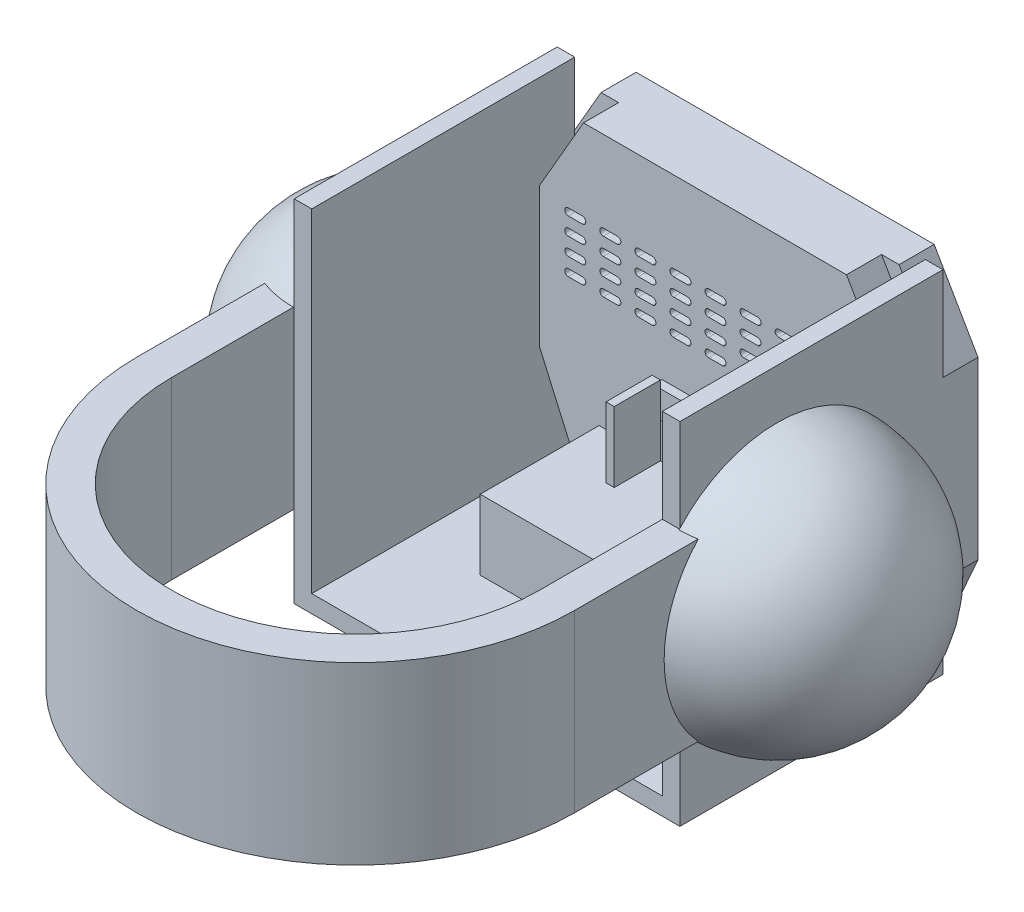
SolidWorks part; units mm, degrees
ref_plane "前视基准面" through (0, 0, 0) normal (0, 0, 1) x (1, 0, 0)
ref_plane "上视基准面" through (0, 0, 0) normal (0, 1, 0) x (1, 0, 0)
ref_plane "右视基准面" through (0, 0, 0) normal (1, 0, 0) x (0, 0, -1)
sketch "草图1" plane through (0, 0, 0) normal (0, 0, 1) x (1, 0, 0)
  line L0 (25, 43.3013) -> (175, 43.3013)
  line L1 (175, 43.3013) -> (200, 0)
  line L2 (200, 0) -> (200, -80)
  line L4 (0, 0) -> (0, -80)
  line L5 (25, 43.3013) -> (0, 0)
  line L6 (175, -136.6987) -> (200, -80)
  line L7 (25, -136.6987) -> (175, -136.6987)
  line L8 (25, -136.6987) -> (0, -80)
  point P10 (200, -40)
  point P13 (0, -40)
  dimension "D1" = 150
  dimension "D2" = 25
  dimension "D3" = 25
  dimension "D4" = 180
  dimension "D5" = 80
  dimension "D6" = 50
  dimension "D7" = 56.6987
extrude "凸台-拉伸1" add sketch "草图1" along normal blind 20
sketch "草图2" plane through (0, 0, 20) normal (0, 0, 1) x (1, 0, 0)
  line L0 (16.3073, -5) -> (24.3073, -5) construction
  line L1 (16.3073, -3) -> (24.3073, -3)
  line L2 (16.3073, -7) -> (24.3073, -7)
  line L3 (36.3073, -5) -> (44.3073, -5) construction
  line L4 (36.3073, -3) -> (44.3073, -3)
  line L5 (36.3073, -7) -> (44.3073, -7)
  line L6 (56.3073, -5) -> (64.3073, -5) construction
  line L7 (56.3073, -3) -> (64.3073, -3)
  line L8 (56.3073, -7) -> (64.3073, -7)
  line L9 (76.3073, -5) -> (84.3073, -5) construction
  line L10 (76.3073, -3) -> (84.3073, -3)
  line L11 (76.3073, -7) -> (84.3073, -7)
  line L12 (96.3073, -5) -> (104.3073, -5) construction
  line L13 (96.3073, -3) -> (104.3073, -3)
  line L14 (96.3073, -7) -> (104.3073, -7)
  line L15 (116.3073, -5) -> (124.3073, -5) construction
  line L16 (116.3073, -3) -> (124.3073, -3)
  line L17 (116.3073, -7) -> (124.3073, -7)
  line L18 (136.3073, -5) -> (144.3073, -5) construction
  line L19 (136.3073, -3) -> (144.3073, -3)
  line L20 (136.3073, -7) -> (144.3073, -7)
  line L21 (156.3073, -5) -> (164.3073, -5) construction
  line L22 (156.3073, -3) -> (164.3073, -3)
  line L23 (156.3073, -7) -> (164.3073, -7)
  line L24 (176.3073, -5) -> (184.3073, -5) construction
  line L25 (176.3073, -3) -> (184.3073, -3)
  line L26 (176.3073, -7) -> (184.3073, -7)
  line L27 (16.3073, -15) -> (24.3073, -15) construction
  line L28 (16.3073, -13) -> (24.3073, -13)
  line L29 (16.3073, -17) -> (24.3073, -17)
  line L30 (16.3073, -25) -> (24.3073, -25) construction
  line L31 (16.3073, -23) -> (24.3073, -23)
  line L32 (16.3073, -27) -> (24.3073, -27)
  line L33 (16.3073, -35) -> (24.3073, -35) construction
  line L34 (16.3073, -33) -> (24.3073, -33)
  line L35 (16.3073, -37) -> (24.3073, -37)
  line L36 (36.3073, -13) -> (44.3073, -13)
  line L37 (36.3073, -17) -> (44.3073, -17)
  line L38 (36.3073, -15) -> (44.3073, -15) construction
  line L39 (36.3073, -25) -> (44.3073, -25) construction
  line L40 (36.3073, -23) -> (44.3073, -23)
  line L41 (36.3073, -27) -> (44.3073, -27)
  line L42 (36.3073, -35) -> (44.3073, -35) construction
  line L43 (36.3073, -33) -> (44.3073, -33)
  line L44 (36.3073, -37) -> (44.3073, -37)
  line L45 (56.3073, -13) -> (64.3073, -13)
  line L46 (56.3073, -17) -> (64.3073, -17)
  line L47 (56.3073, -15) -> (64.3073, -15) construction
  line L48 (56.3073, -25) -> (64.3073, -25) construction
  line L49 (56.3073, -23) -> (64.3073, -23)
  line L50 (56.3073, -27) -> (64.3073, -27)
  line L51 (56.3073, -35) -> (64.3073, -35) construction
  line L52 (56.3073, -33) -> (64.3073, -33)
  line L53 (56.3073, -37) -> (64.3073, -37)
  line L54 (76.3073, -13) -> (84.3073, -13)
  line L55 (76.3073, -17) -> (84.3073, -17)
  line L56 (76.3073, -15) -> (84.3073, -15) construction
  line L57 (76.3073, -25) -> (84.3073, -25) construction
  line L58 (76.3073, -23) -> (84.3073, -23)
  line L59 (76.3073, -27) -> (84.3073, -27)
  line L60 (76.3073, -35) -> (84.3073, -35) construction
  line L61 (76.3073, -33) -> (84.3073, -33)
  line L62 (76.3073, -37) -> (84.3073, -37)
  line L63 (96.3073, -13) -> (104.3073, -13)
  line L64 (96.3073, -17) -> (104.3073, -17)
  line L65 (96.3073, -15) -> (104.3073, -15) construction
  line L66 (96.3073, -25) -> (104.3073, -25) construction
  line L67 (96.3073, -23) -> (104.3073, -23)
  line L68 (96.3073, -27) -> (104.3073, -27)
  line L69 (96.3073, -35) -> (104.3073, -35) construction
  line L70 (96.3073, -33) -> (104.3073, -33)
  line L71 (96.3073, -37) -> (104.3073, -37)
  line L72 (116.3073, -13) -> (124.3073, -13)
  line L73 (116.3073, -17) -> (124.3073, -17)
  line L74 (116.3073, -15) -> (124.3073, -15) construction
  line L75 (116.3073, -25) -> (124.3073, -25) construction
  line L76 (116.3073, -23) -> (124.3073, -23)
  line L77 (116.3073, -27) -> (124.3073, -27)
  line L78 (116.3073, -35) -> (124.3073, -35) construction
  line L79 (116.3073, -33) -> (124.3073, -33)
  line L80 (116.3073, -37) -> (124.3073, -37)
  line L81 (136.3073, -13) -> (144.3073, -13)
  line L82 (136.3073, -17) -> (144.3073, -17)
  line L83 (136.3073, -15) -> (144.3073, -15) construction
  line L84 (136.3073, -25) -> (144.3073, -25) construction
  line L85 (136.3073, -23) -> (144.3073, -23)
  line L86 (136.3073, -27) -> (144.3073, -27)
  line L87 (136.3073, -35) -> (144.3073, -35) construction
  line L88 (136.3073, -33) -> (144.3073, -33)
  line L89 (136.3073, -37) -> (144.3073, -37)
  line L90 (156.3073, -13) -> (164.3073, -13)
  line L91 (156.3073, -17) -> (164.3073, -17)
  line L92 (156.3073, -15) -> (164.3073, -15) construction
  line L93 (156.3073, -25) -> (164.3073, -25) construction
  line L94 (156.3073, -23) -> (164.3073, -23)
  line L95 (156.3073, -27) -> (164.3073, -27)
  line L96 (156.3073, -35) -> (164.3073, -35) construction
  line L97 (156.3073, -33) -> (164.3073, -33)
  line L98 (156.3073, -37) -> (164.3073, -37)
  line L99 (176.3073, -13) -> (184.3073, -13)
  line L100 (176.3073, -17) -> (184.3073, -17)
  line L101 (176.3073, -15) -> (184.3073, -15) construction
  line L102 (176.3073, -25) -> (184.3073, -25) construction
  line L103 (176.3073, -23) -> (184.3073, -23)
  line L104 (176.3073, -27) -> (184.3073, -27)
  line L105 (176.3073, -35) -> (184.3073, -35) construction
  line L106 (176.3073, -33) -> (184.3073, -33)
  line L107 (176.3073, -37) -> (184.3073, -37)
  line L108 (0, 0) -> (0, -80) construction
  arc A0 (16.3073, -3) -> (16.3073, -7) centre (16.3073, -5) ccw
  arc A1 (24.3073, -7) -> (24.3073, -3) centre (24.3073, -5) ccw
  arc A2 (36.3073, -3) -> (36.3073, -7) centre (36.3073, -5) ccw
  arc A3 (44.3073, -7) -> (44.3073, -3) centre (44.3073, -5) ccw
  arc A4 (56.3073, -3) -> (56.3073, -7) centre (56.3073, -5) ccw
  arc A5 (64.3073, -7) -> (64.3073, -3) centre (64.3073, -5) ccw
  arc A6 (76.3073, -3) -> (76.3073, -7) centre (76.3073, -5) ccw
  arc A7 (84.3073, -7) -> (84.3073, -3) centre (84.3073, -5) ccw
  arc A8 (96.3073, -3) -> (96.3073, -7) centre (96.3073, -5) ccw
  arc A9 (104.3073, -7) -> (104.3073, -3) centre (104.3073, -5) ccw
  arc A10 (116.3073, -3) -> (116.3073, -7) centre (116.3073, -5) ccw
  arc A11 (124.3073, -7) -> (124.3073, -3) centre (124.3073, -5) ccw
  arc A12 (136.3073, -3) -> (136.3073, -7) centre (136.3073, -5) ccw
  arc A13 (144.3073, -7) -> (144.3073, -3) centre (144.3073, -5) ccw
  arc A14 (156.3073, -3) -> (156.3073, -7) centre (156.3073, -5) ccw
  arc A15 (164.3073, -7) -> (164.3073, -3) centre (164.3073, -5) ccw
  arc A16 (176.3073, -3) -> (176.3073, -7) centre (176.3073, -5) ccw
  arc A17 (184.3073, -7) -> (184.3073, -3) centre (184.3073, -5) ccw
  arc A18 (16.3073, -13) -> (16.3073, -17) centre (16.3073, -15) ccw
  arc A19 (24.3073, -17) -> (24.3073, -13) centre (24.3073, -15) ccw
  arc A20 (16.3073, -23) -> (16.3073, -27) centre (16.3073, -25) ccw
  arc A21 (24.3073, -27) -> (24.3073, -23) centre (24.3073, -25) ccw
  arc A22 (16.3073, -33) -> (16.3073, -37) centre (16.3073, -35) ccw
  arc A23 (24.3073, -37) -> (24.3073, -33) centre (24.3073, -35) ccw
  arc A24 (44.3073, -17) -> (44.3073, -13) centre (44.3073, -15) ccw
  arc A25 (36.3073, -13) -> (36.3073, -17) centre (36.3073, -15) ccw
  arc A26 (36.3073, -23) -> (36.3073, -27) centre (36.3073, -25) ccw
  arc A27 (44.3073, -27) -> (44.3073, -23) centre (44.3073, -25) ccw
  arc A28 (36.3073, -33) -> (36.3073, -37) centre (36.3073, -35) ccw
  arc A29 (44.3073, -37) -> (44.3073, -33) centre (44.3073, -35) ccw
  arc A30 (64.3073, -17) -> (64.3073, -13) centre (64.3073, -15) ccw
  arc A31 (56.3073, -13) -> (56.3073, -17) centre (56.3073, -15) ccw
  arc A32 (56.3073, -23) -> (56.3073, -27) centre (56.3073, -25) ccw
  arc A33 (64.3073, -27) -> (64.3073, -23) centre (64.3073, -25) ccw
  arc A34 (56.3073, -33) -> (56.3073, -37) centre (56.3073, -35) ccw
  arc A35 (64.3073, -37) -> (64.3073, -33) centre (64.3073, -35) ccw
  arc A36 (84.3073, -17) -> (84.3073, -13) centre (84.3073, -15) ccw
  arc A37 (76.3073, -13) -> (76.3073, -17) centre (76.3073, -15) ccw
  arc A38 (76.3073, -23) -> (76.3073, -27) centre (76.3073, -25) ccw
  arc A39 (84.3073, -27) -> (84.3073, -23) centre (84.3073, -25) ccw
  arc A40 (76.3073, -33) -> (76.3073, -37) centre (76.3073, -35) ccw
  arc A41 (84.3073, -37) -> (84.3073, -33) centre (84.3073, -35) ccw
  arc A42 (104.3073, -17) -> (104.3073, -13) centre (104.3073, -15) ccw
  arc A43 (96.3073, -13) -> (96.3073, -17) centre (96.3073, -15) ccw
  arc A44 (96.3073, -23) -> (96.3073, -27) centre (96.3073, -25) ccw
  arc A45 (104.3073, -27) -> (104.3073, -23) centre (104.3073, -25) ccw
  arc A46 (96.3073, -33) -> (96.3073, -37) centre (96.3073, -35) ccw
  arc A47 (104.3073, -37) -> (104.3073, -33) centre (104.3073, -35) ccw
  arc A48 (124.3073, -17) -> (124.3073, -13) centre (124.3073, -15) ccw
  arc A49 (116.3073, -13) -> (116.3073, -17) centre (116.3073, -15) ccw
  arc A50 (116.3073, -23) -> (116.3073, -27) centre (116.3073, -25) ccw
  arc A51 (124.3073, -27) -> (124.3073, -23) centre (124.3073, -25) ccw
  arc A52 (116.3073, -33) -> (116.3073, -37) centre (116.3073, -35) ccw
  arc A53 (124.3073, -37) -> (124.3073, -33) centre (124.3073, -35) ccw
  arc A54 (144.3073, -17) -> (144.3073, -13) centre (144.3073, -15) ccw
  arc A55 (136.3073, -13) -> (136.3073, -17) centre (136.3073, -15) ccw
  arc A56 (136.3073, -23) -> (136.3073, -27) centre (136.3073, -25) ccw
  arc A57 (144.3073, -27) -> (144.3073, -23) centre (144.3073, -25) ccw
  arc A58 (136.3073, -33) -> (136.3073, -37) centre (136.3073, -35) ccw
  arc A59 (144.3073, -37) -> (144.3073, -33) centre (144.3073, -35) ccw
  arc A60 (164.3073, -17) -> (164.3073, -13) centre (164.3073, -15) ccw
  arc A61 (156.3073, -13) -> (156.3073, -17) centre (156.3073, -15) ccw
  arc A62 (156.3073, -23) -> (156.3073, -27) centre (156.3073, -25) ccw
  arc A63 (164.3073, -27) -> (164.3073, -23) centre (164.3073, -25) ccw
  arc A64 (156.3073, -33) -> (156.3073, -37) centre (156.3073, -35) ccw
  arc A65 (164.3073, -37) -> (164.3073, -33) centre (164.3073, -35) ccw
  arc A66 (184.3073, -17) -> (184.3073, -13) centre (184.3073, -15) ccw
  arc A67 (176.3073, -13) -> (176.3073, -17) centre (176.3073, -15) ccw
  arc A68 (176.3073, -23) -> (176.3073, -27) centre (176.3073, -25) ccw
  arc A69 (184.3073, -27) -> (184.3073, -23) centre (184.3073, -25) ccw
  arc A70 (176.3073, -33) -> (176.3073, -37) centre (176.3073, -35) ccw
  arc A71 (184.3073, -37) -> (184.3073, -33) centre (184.3073, -35) ccw
  point P2 (20.3073, -5)
  point P14 (40.3073, -5)
  point P21 (60.3073, -5)
  point P28 (80.3073, -5)
  point P35 (100.3073, -5)
  point P42 (120.3073, -5)
  point P49 (140.3073, -5)
  point P56 (160.3073, -5)
  point P63 (180.3073, -5)
  point P69 (20.3073, -15)
  point P76 (20.3073, -25)
  point P83 (20.3073, -35)
  point P90 (40.3073, -15)
  point P97 (40.3073, -25)
  point P104 (40.3073, -35)
  point P111 (60.3073, -15)
  point P118 (60.3073, -25)
  point P125 (60.3073, -35)
  point P132 (80.3073, -15)
  point P139 (80.3073, -25)
  point P146 (80.3073, -35)
  point P153 (100.3073, -15)
  point P160 (100.3073, -25)
  point P167 (100.3073, -35)
  point P174 (120.3073, -15)
  point P181 (120.3073, -25)
  point P188 (120.3073, -35)
  point P195 (140.3073, -15)
  point P202 (140.3073, -25)
  point P209 (140.3073, -35)
  point P216 (160.3073, -15)
  point P223 (160.3073, -25)
  point P230 (160.3073, -35)
  point P237 (180.3073, -15)
  point P244 (180.3073, -25)
  point P251 (180.3073, -35)
  dimension "D1" = 8
  dimension "D2" = 4
  dimension "D3" = 5
  dimension "D7" = 20.3073
  dimension "D8" = 20
  dimension "D9" = 20
  dimension "D10" = 10
  dimension "D4" = 9
  dimension "D5" = 4
  dimension "D6" = 9
extrude "切除-拉伸1" cut sketch "草图2" against normal through all
sketch "草图4" plane through (0, 43.3013, 0) normal (0, 1, 0) x (1, 0, 0)
  line L0 (200, -20) -> (200, 0) construction
  line L1 (0, 0) -> (200, 0)
  line L2 (0, 0) -> (0, -150)
  line L3 (0, -150) -> (200, -150)
  line L4 (200, 0) -> (200, -150)
  dimension "D1" = 150
sketch "草图5" plane through (0, 0, 0) normal (-1, 0, 0) x (0, 0, 1)
  line L1 (0, 53.3013) -> (150, 53.3013)
  line L2 (0, 53.3013) -> (0, -136.6987)
  line L3 (0, -136.6987) -> (150, -136.6987)
  line L5 (20, -136.6987) -> (0, -136.6987) construction
  line L6 (0, -80) -> (0, -136.6987) construction
  line L7 (150, 53.3013) -> (150, -136.6987)
  dimension "D1" = 190
  dimension "D2" = 150
sketch "草图6" plane through (200, 0, 0) normal (1, 0, 0) x (0, 0, -1)
  line L0 (-20, -136.6987) -> (0, -136.6987) construction
  line L1 (-150, 53.3013) -> (0, 53.3013)
  line L2 (-150, 53.3013) -> (-150, -136.6987)
  line L3 (-150, -136.6987) -> (0, -136.6987)
  line L4 (0, 53.3013) -> (0, -136.6987)
  line L9 (0, -80) -> (0, 0) construction
  dimension "D1" = 150
  dimension "D2" = 190
extrude "凸台-拉伸8" add sketch "草图5" along normal blind 10
extrude "凸台-拉伸5" add sketch "草图6" along normal blind 10
sketch "草图7" plane through (0, 0, 0) normal (0, 1, 0) x (1, 0, 0)
  line L0 (-9.9985, -94.5873) -> (-29.9585, -94.5873)
  line L2 (-29.9585, -94.5873) -> (-29.9585, -220)
  line L3 (-9.9985, -114.5458) -> (-10, -114.5458)
  line L4 (-10, -114.5458) -> (-10, -220)
  line L5 (219.9585, -94.5873) -> (219.9585, -220)
  line L6 (199.9985, -94.5873) -> (219.9585, -94.5873)
  line L7 (200, -114.5458) -> (200, -220)
  line L8 (199.9985, -114.5458) -> (200, -114.5458)
  line L9 (-9.9985, -114.5458) -> (-9.9985, -94.5873)
  line L10 (200, -114.5458) -> (199.9985, -94.5873)
  line L11 (200, 0) -> (200, -150) construction
  line L12 (-10, -150) -> (-10, 0) construction
  line L13 (0, -150) -> (200, -150) construction
  arc A1 (-29.9585, -220) -> (219.9585, -220) centre (95, -220) ccw
  arc A2 (-10, -220) -> (200, -220) centre (95, -220) ccw
  point P9 (100, -200.4127)
  dimension "D1" = 19.96
  dimension "D6" = 105
  dimension "D4" = 70
  dimension "D3" = 19.96
  dimension "D2" = 125.4127
  dimension "D5" = 249.917
extrude "凸台-拉伸6" add sketch "草图7" against normal blind 100 contours A2 L4 L9 L0 L2 A1 L5 L6 L10 L7 region at (-13.5361, 0, 104.5665)
sketch "草图8" plane through (0, -136.6987, 0) normal (0, -1, 0) x (1, 0, 0)
  line L1 (-10, 150) -> (210, 150)
  line L3 (-10, 0) -> (210, 0)
  line L4 (210, 150) -> (210, 0)
  line L5 (0, 150) -> (200, 150) construction
  line L7 (-10, 0) -> (-10, 150)
extrude "凸台-拉伸7" add sketch "草图8" along normal blind 10
sketch "草图9" plane through (0, 0, 0) normal (0, 0, -1) x (-1, 0, 0)
  line L0 (-210, 0) -> (-210, -100)
  line L1 (-210, -100) -> (-189.4093, -146.6987)
  line L2 (10, -146.6987) -> (-210, -146.6987) construction
  line L3 (-189.4093, -146.6987) -> (-10.5907, -146.6987)
  line L4 (-200, 0) -> (-175, 43.3013) construction
  line L5 (-210, 0) -> (-185, 43.3013)
  line L6 (0, 43.3013) -> (-200, 43.3013) construction
  line L7 (-185, 43.3013) -> (-15, 43.3013)
  line L8 (10, -100) -> (-10.5907, -146.6987)
  line L9 (10, 0) -> (10, -100)
  line L10 (10, 0) -> (-15, 43.3013)
  line L11 (-175, -136.6987) -> (-200, -80) construction
  line L12 (10, 53.3013) -> (10, -146.6987) construction
  line L13 (0, -80) -> (-25, -136.6987) construction
  point P17 (-100, 43.3013)
extrude "凸台-拉伸9" add sketch "草图9" along normal blind 20
sketch "草图11" plane through (0, 0, -20) normal (0, 0, -1) x (-1, 0, 0)
  arc A0 (-181.4007, -19.8959) -> (-133.3769, -25.2064) centre (-160.1107, -47.1655) cw construction
  arc A1 (-130.3352, -22.708) -> (-183.823, -16.7933) centre (-160.1107, -47.1655) ccw
  arc A2 (-136.4187, -27.7049) -> (-178.9784, -22.9986) centre (-160.1107, -47.1655) ccw
  arc A3 (-136.4187, -27.7049) -> (-130.3352, -22.708) centre (-133.3769, -25.2064) ccw
  arc A4 (-183.823, -16.7933) -> (-178.9784, -22.9986) centre (-181.4007, -19.8959) ccw
  arc A5 (-18.5993, -19.8959) -> (-72.5779, -19.8959) centre (-45.5886, -41.5401) ccw construction
  arc A6 (-75.6487, -17.4333) -> (-15.5285, -17.4333) centre (-45.5886, -41.5401) cw
  arc A7 (-69.5071, -22.3586) -> (-21.6701, -22.3586) centre (-45.5886, -41.5401) cw
  arc A8 (-69.5071, -22.3586) -> (-75.6487, -17.4333) centre (-72.5779, -19.8959) cw
  arc A9 (-15.5285, -17.4333) -> (-21.6701, -22.3586) centre (-18.5993, -19.8959) cw
  arc A10 (-48.7868, -101.4516) -> (-150.1155, -101.4516) centre (-99.4512, -50.7872) cw construction
  arc A15 (-156.3082, -107.6443) -> (-42.5942, -107.6443) centre (-99.4512, -50.7872) ccw
  arc A16 (-143.9228, -95.2589) -> (-54.9795, -95.2589) centre (-99.4512, -50.7872) ccw
  arc A17 (-143.9228, -95.2589) -> (-156.3082, -107.6443) centre (-150.1155, -101.4516) ccw
  arc A18 (-42.5942, -107.6443) -> (-54.9795, -95.2589) centre (-48.7868, -101.4516) ccw
  point P1 (-156.3082, -12.7789)
  point P11 (-99.4512, -122.4374)
  point P15 (-45.5886, -6.944)
extrude "切除-拉伸2" cut sketch "草图11" against normal blind 20
extrude "切除-拉伸3" cut sketch "草图2<3>" along normal blind 20 and the other way through all
sketch "草图2<3>" plane through (0, 0, 20) normal (0, 0, 1) x (1, 0, 0) same geometry as "草图2"
sketch "草图12" plane through (0, -136.6987, 0) normal (0, 1, 0) x (1, 0, 0)
  line L1 (38.9432, -25.0508) -> (163.3535, -25.0508)
  line L2 (38.9432, -25.0508) -> (38.9432, -92.8633)
  line L3 (38.9432, -92.8633) -> (163.3535, -92.8633)
  line L4 (163.3535, -25.0508) -> (163.3535, -92.8633)
extrude "凸台-拉伸10" add sketch "草图12" along normal blind 40
sketch "草图13" plane through (0, -96.6987, 0) normal (0, 1, 0) x (1, 0, 0)
  line L0 (163.3535, -25.0508) -> (38.9432, -25.0508) construction
  line L1 (69.2096, -25.0508) -> (73.8988, -25.0508)
  line L2 (69.2096, -25.0508) -> (69.2096, -51.3822)
  line L3 (69.2096, -51.3822) -> (73.8988, -51.3822)
  line L4 (73.8988, -25.0508) -> (73.8988, -51.3822)
extrude "凸台-拉伸11" add sketch "草图13" along normal blind 40
sketch "草图14" plane through (0, 0, 20) normal (0, 0, 1) x (1, 0, 0)
  line L1 (69.6868, -61.0828) -> (90.224, -61.0828)
  line L2 (69.6868, -61.0828) -> (69.6868, -76.5748)
  line L3 (69.6868, -76.5748) -> (90.224, -76.5748)
  line L4 (90.224, -61.0828) -> (90.224, -76.5748)
extrude "凸台-拉伸12" add sketch "草图14" along normal blind 5
sketch "草图16" plane through (0, 0, 25) normal (0, 0, 1) x (1, 0, 0)
  circle A0 centre (81.6268, -68.3972) radius 2.3982
extrude "凸台-拉伸13" add sketch "草图16" along normal blind 1
sketch "草图18" plane through (210, 0, 0) normal (1, 0, 0) x (0, 0, -1)
  circle A0 centre (-25.9932, -109.6666) radius 9.4843
extrude "切除-拉伸4" cut sketch "草图18" against normal blind 10
sketch "草图19" plane through (210, 0, 0) normal (1, 0, 0) x (0, 0, -1)
  line L0 (-169.5873, -50) -> (-19.5873, -50)
  line L2 (-94.5873, 0) -> (-94.5873, -100) construction
  arc A0 (-169.5873, -50) -> (-19.5873, -50) centre (-94.5873, -50) cw
  point P11 (-94.5873, -50)
  dimension "D1" = 150
revolve "旋转1" add sketch "草图19" angle 180 about L0
sketch "草图20" plane through (-10, 0, 0) normal (-1, 0, 0) x (0, 0, 1)
  line L0 (169.5873, -50) -> (19.5873, -50)
  line L1 (94.5873, 0) -> (94.5873, -100) construction
  arc A0 (19.5873, -50) -> (169.5873, -50) centre (94.5873, -50) cw
  point P8 (94.5873, -50)
  dimension "D1" = 150
revolve "旋转2" add sketch "草图20" angle 180 about L0 reverse direction yes
